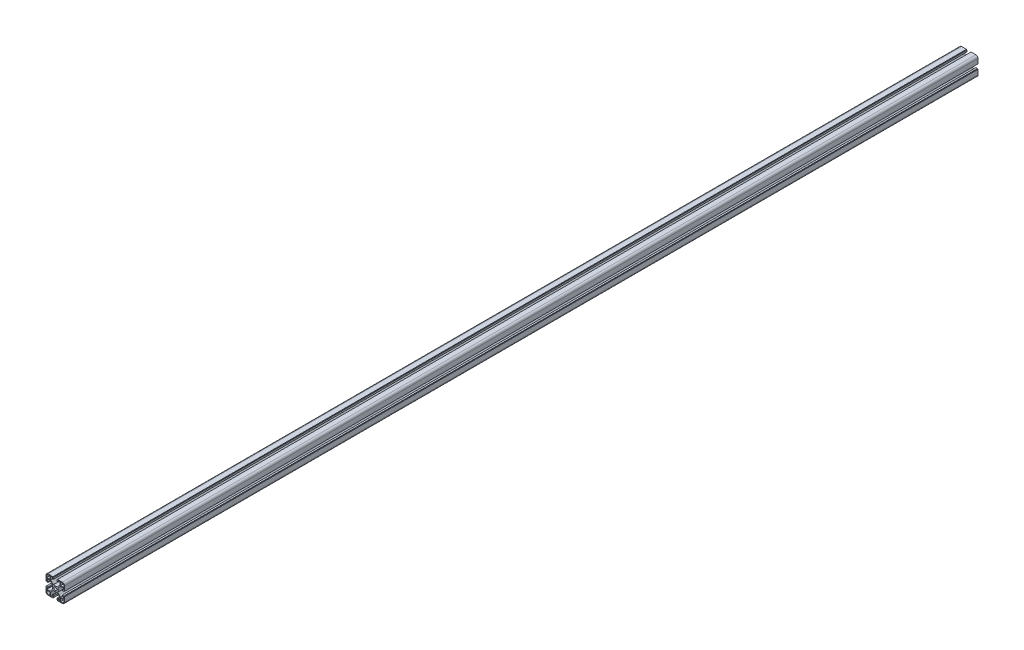
SolidWorks part; units mm, degrees
material "6061-T6 (SS)"
ref_plane "Front Plane" through (0, 0, 0) normal (0, 0, 1) x (1, 0, 0)
ref_plane "Top Plane" through (0, 0, 0) normal (0, 1, 0) x (1, 0, 0)
ref_plane "Right Plane" through (0, 0, 0) normal (1, 0, 0) x (0, 0, -1)
sketch "Sketch1" plane through (0, 0, 0) normal (0, 0, 1) x (1, 0, 0)
  line L0 (3.4, 0) -> (5.5, 0)
  line L1 (10.19, 11.69) -> (4, 5.5)
  line L2 (11.69, 10.19) -> (5.5, 4)
  line L3 (18.2, 10.19) -> (11.69, 10.19)
  line L4 (18.2, 10.19) -> (18.2, 6.3)
  line L5 (18.2, 6.3) -> (15.5, 6.3)
  line L6 (15.5, 6.3) -> (15.5, 4)
  line L7 (15.5, 4) -> (19, 4)
  line L8 (19, 4) -> (19, 5)
  line L9 (19, 5) -> (20, 5)
  line L10 (20, 5) -> (20, 15.5)
  line L11 (15.5, 20) -> (5, 20)
  line L12 (18.5, 11.69) -> (18.5, 15.5)
  line L13 (15.5, 18.5) -> (11.69, 18.5)
  line L14 (11.69, 11.69) -> (11.69, 18.5)
  line L15 (0, 3.4) -> (0, 5.5)
  line L16 (4, 5.5) -> (0, 5.5)
  line L17 (5, 20) -> (5, 19)
  line L18 (5.5, 0) -> (5.5, 4)
  line L19 (5, 19) -> (4, 19)
  line L20 (4, 19) -> (4, 15.5)
  line L21 (4, 15.5) -> (6.3, 15.5)
  line L22 (10.19, 11.69) -> (10.19, 18.2)
  line L23 (11.69, 11.69) -> (18.5, 11.69)
  line L24 (6.3, 18.2) -> (6.3, 15.5)
  line L25 (10.19, 18.2) -> (6.3, 18.2)
  arc A0 (20, 15.5) -> (15.5, 20) centre (15.5, 15.5) ccw
  arc A1 (18.5, 15.5) -> (15.5, 18.5) centre (15.5, 15.5) ccw
  arc A2 (3.4, 0) -> (0, 3.4) centre (0, 0) ccw
  point P4 (0, 4.45)
  dimension "D3" = 4.5
  dimension "D18" = 1.5
  dimension "D9" = 3.4
  dimension "D20" = 1.8
  dimension "D25" = 3
  dimension "D1" = 5.5
  dimension "D2" = 1.5
  dimension "D4" = 14.5
  dimension "D5" = 1.5
  dimension "D6" = 2.1
  dimension "D7" = 2.3
  dimension "D8" = 1.8
  dimension "D10" = 6.81
  dimension "D11" = 2.1
  dimension "D12" = 1
  dimension "D13" = 4.5
  dimension "D14" = 45
  dimension "D15" = 14.5
  dimension "D16" = 1
  dimension "D17" = 1.5
  dimension "D19" = 6.81
  dimension "D21" = 4.5
  dimension "D22" = 2.3
  dimension "D23" = 1
  dimension "D24" = 1
  dimension "D26" = 8.754
  dimension "D27" = 8.754
  dimension "D28" = 4
  dimension "D29" = 4
extrude "Boss-Extrude1" add sketch "Sketch1" along normal blind 1980
mirror "Mirror1" about plane through (0, 0, 0) normal (0, 1, 0) of "Boss-Extrude1"
mirror "Mirror2" about plane through (0, 0, 0) normal (1, 0, 0) of "Boss-Extrude1"
mirror "Mirror3" about plane through (0, 0, 0) normal (0, 1, 0) of "Mirror2"
